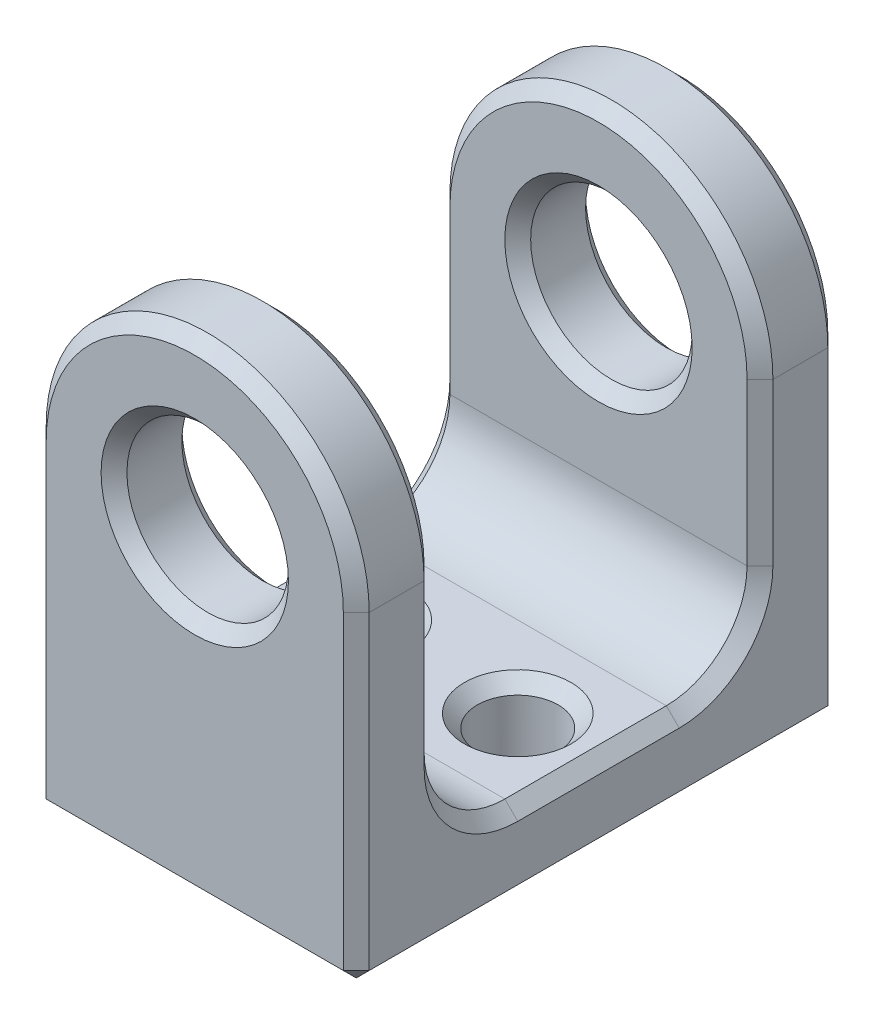
SolidWorks part; units mm, degrees
ref_plane "Front Plane" through (0, 0, 0) normal (0, 0, 1) x (1, 0, 0)
ref_plane "Top Plane" through (0, 0, 0) normal (0, 1, 0) x (1, 0, 0)
ref_plane "Right Plane" through (0, 0, 0) normal (1, 0, 0) x (0, 0, -1)
sketch "Sketch1" plane through (0, 0, 0) normal (0, 0, 1) x (1, 0, 0)
  line L2 (-6.35, 0) -> (-6.35, -12.7)
  line L3 (-6.35, -12.7) -> (6.35, -12.7)
  line L4 (6.35, 0) -> (6.35, -12.7)
  circle A0 centre (0, 0) radius 3.175
  arc A1 (6.35, 0) -> (-6.35, 0) centre (0, 0) ccw
  point P8 (0, -12.7)
  dimension "D1" = 6.35
  dimension "D4" = 12.7
  dimension "D2" = 12.7
extrude "Boss-Extrude1" add sketch "Sketch1" along normal mid plane 19.05
sketch "Sketch2" plane through (0, 0, 0) normal (1, 0, 0) x (0, 0, -1)
  line L1 (-6.35, 6.35) -> (6.35, 6.35)
  line L2 (-6.35, 6.35) -> (-6.35, -9.525)
  line L3 (-6.35, -9.525) -> (6.35, -9.525)
  line L4 (6.35, 6.35) -> (6.35, -9.525)
  line L5 (-9.525, -12.7) -> (9.525, -12.7) construction
  line L6 (9.525, 6.35) -> (-9.525, 6.35) construction
  point P6 (0, 6.35)
  dimension "D1" = 12.7
  dimension "D2" = 3.175
extrude "Cut-Extrude1" cut sketch "Sketch2" against normal through all both and the other way through all contours L1 L4 L3 L2
hole_wizard "1/8 (0.125) Diameter Hole1" positions "Sketch3" profile "Sketch4" hole size "1/8" standard "ANSI Inch" end condition through all
sketch "Sketch3" plane through (0, -9.525, 0) normal (0, 1, 0) x (1, 0, 0)
  line L0 (-3.175, 0) -> (3.175, 0) construction
  point P0 (-3.175, 0)
  point P2 (3.175, 0)
  dimension "D1" = 6.35
sketch "Sketch4" plane through (-3.175, -9.525, 0) normal (1, 0, 0) x (0, 0, 1)
  line L0 (0, 0) -> (0, 3.175)
  line L1 (0, 3.175) -> (1.5875, 3.175)
  line L2 (1.5875, 3.175) -> (1.5875, 0)
  line L5 (1.5875, 0) -> (0, 0)
  line L11 (0, -6.35) -> (0, 107.95) construction
  dimension "Thru Hole Dia." = 3.175
  dimension "Thru Hole Depth" = 3.175
ref_plane "Plane1" through (0, 6.35, 0) normal (0, 1, 0) x (1, 0, 0)
fillet "Fillet2" radius 3.175 2 edges at (0, -9.525, -6.35) (0, -9.525, 6.35)
chamfer "Chamfer1" distance 0.508 angle 45 30 edges at (6.35, -6.35, -9.525) (-6.35, -6.35, -9.525) (-6.35, -3.175, -6.35) (6.35, -3.175, -6.35) (-6.35, -9.525, 0) (6.35, -9.525, 0) (-6.35, -3.175, 6.35) (6.35, -3.175, 6.35) (6.35, -6.35, 9.525) (-6.35, -6.35, 9.525) (0, -12.7, -9.525) (-6.35, -12.7, 0) (0, -12.7, 9.525) (6.35, -12.7, 0) (3.175, 0, -9.525) (0, -3.175, -6.35) (0, -3.175, 6.35) (3.175, 0, 9.525) (3.175, -12.7, 1.5875) (-3.175, -12.7, 1.5875) (3.175, -9.525, 1.5875) (-3.175, -9.525, 1.5875) (0, 6.35, 6.35) (0, 6.35, -6.35) (0, 6.35, 9.525) (0, 6.35, -9.525) (6.35, -8.5951, 5.4201) (6.35, -8.5951, -5.4201) (-6.35, -8.5951, 5.4201) (-6.35, -8.5951, -5.4201)
